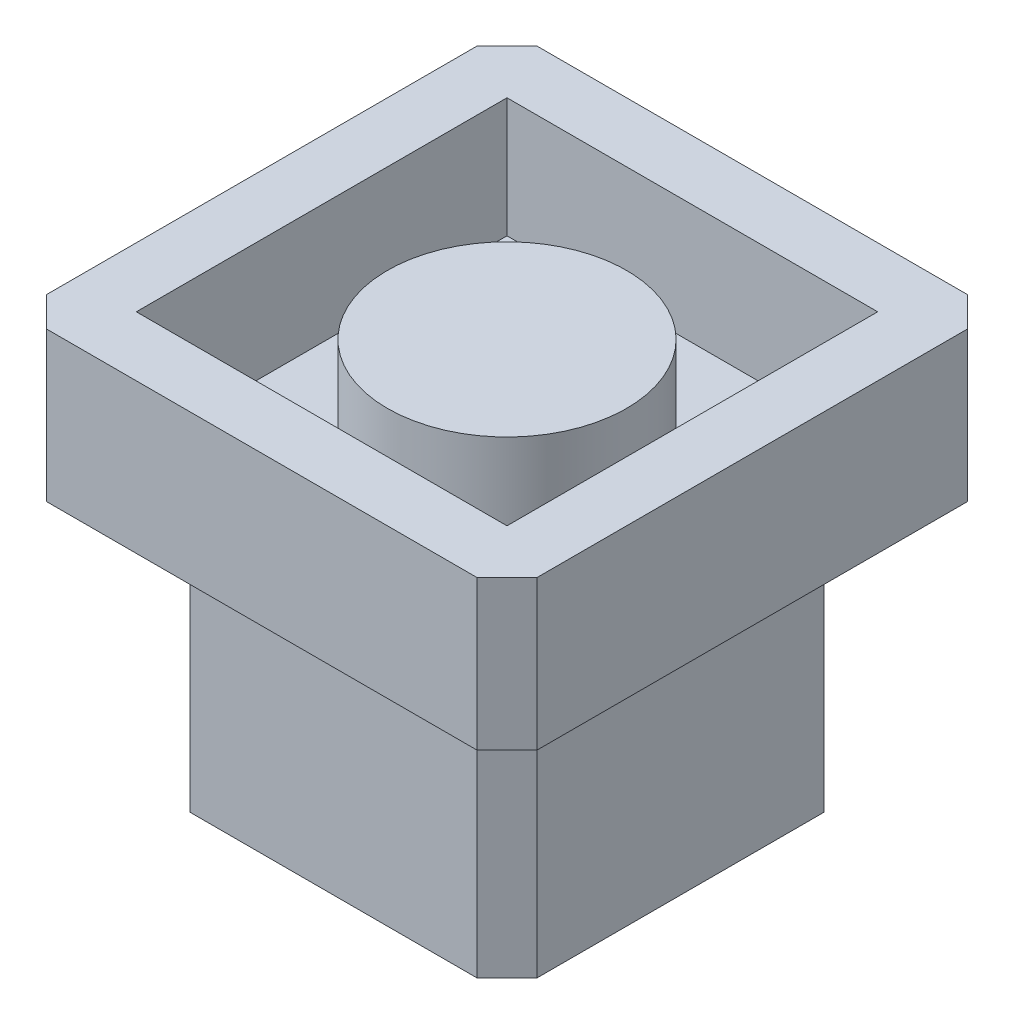
SolidWorks part; units mm, degrees
ref_plane "Front Plane" through (0, 0, 0) normal (0, 0, 1) x (1, 0, 0)
ref_plane "Top Plane" through (0, 0, 0) normal (0, 1, 0) x (1, 0, 0)
ref_plane "Right Plane" through (0, 0, 0) normal (1, 0, 0) x (0, 0, -1)
sketch "Sketch1" plane through (0, 0, 0) normal (0, 1, 0) x (1, 0, 0)
  line L0 (-4.1, 4.1) -> (-4.1, -4.1)
  line L1 (-3.1, 3.1) -> (3.1, 3.1)
  line L2 (-3.1, 3.1) -> (-3.1, -3.1)
  line L3 (-3.1, -3.1) -> (3.1, -3.1)
  line L4 (3.1, 3.1) -> (3.1, -3.1)
  line L5 (-3.1, 3.1) -> (3.1, -3.1) construction
  line L6 (-3.1, -3.1) -> (3.1, 3.1) construction
  line L7 (-4.1, -4.1) -> (4.1, -4.1)
  line L8 (4.1, 4.1) -> (4.1, -4.1)
  line L9 (-4.1, 4.1) -> (4.1, 4.1)
  circle A1 centre (0, 0) radius 2
  dimension "D1" = 4
  dimension "D2" = 6.2
  dimension "D3" = 1
extrude "Boss-Extrude1" add sketch "Sketch1" along normal blind 1.6 contours A1 region at (0, 0, 0)
extrude "Boss-Extrude2" add sketch "Sketch1<3>" along normal blind 2 separate body contours L9 L0 L7 L8 L1 L4 L3 L2 region at (0, 0, -3.984)
sketch "Sketch1<3>" plane through (0, 0, 0) normal (0, 1, 0) x (1, 0, 0) same geometry as "Sketch1"
extrude "Boss-Extrude3" add sketch "Sketch1<4>" against normal blind 0.5 contours L9 L0 L7 L8 L1 L4 L3 L2 | L4 L1 L2 L3 A1 | A1 region at (0, 0, -3.984) region at (0, 0, -3.0123) region at (0, 0, 0)
sketch "Sketch1<4>" plane through (0, 0, 0) normal (0, 1, 0) x (1, 0, 0) same geometry as "Sketch1"
sketch "Sketch3" plane through (0, -0.5, 0) normal (0, -1, 0) x (1, 0, 0)
  line L1 (-2.9, 2.9) -> (2.9, 2.9)
  line L2 (-2.9, 2.9) -> (-2.9, -2.9)
  line L3 (-2.9, -2.9) -> (2.9, -2.9)
  line L4 (2.9, 2.9) -> (2.9, -2.9)
  line L5 (-2.9, 2.9) -> (2.9, -2.9) construction
  line L6 (-2.9, -2.9) -> (2.9, 2.9) construction
  point P0 (0, 0)
  dimension "D1" = 5.8
  dimension "D2" = 5.8
extrude "Boss-Extrude4" add sketch "Sketch3" along normal blind 4.5
chamfer "Chamfer1" distance 0.5 angle 45 8 edges at (-4.1, 0.75, -4.1) (4.1, 0.75, -4.1) (-4.1, 0.75, 4.1) (4.1, 0.75, 4.1) (-2.9, -2.75, 2.9) (2.9, -2.75, 2.9) (-2.9, -2.75, -2.9) (2.9, -2.75, -2.9)
sketch "Sketch4" plane through (0, -5, 0) normal (0, -1, 0) x (1, 0, 0)
  text T1 "C"
extrude "Cut-Extrude1" cut sketch "Sketch4" against normal blind 0.2
